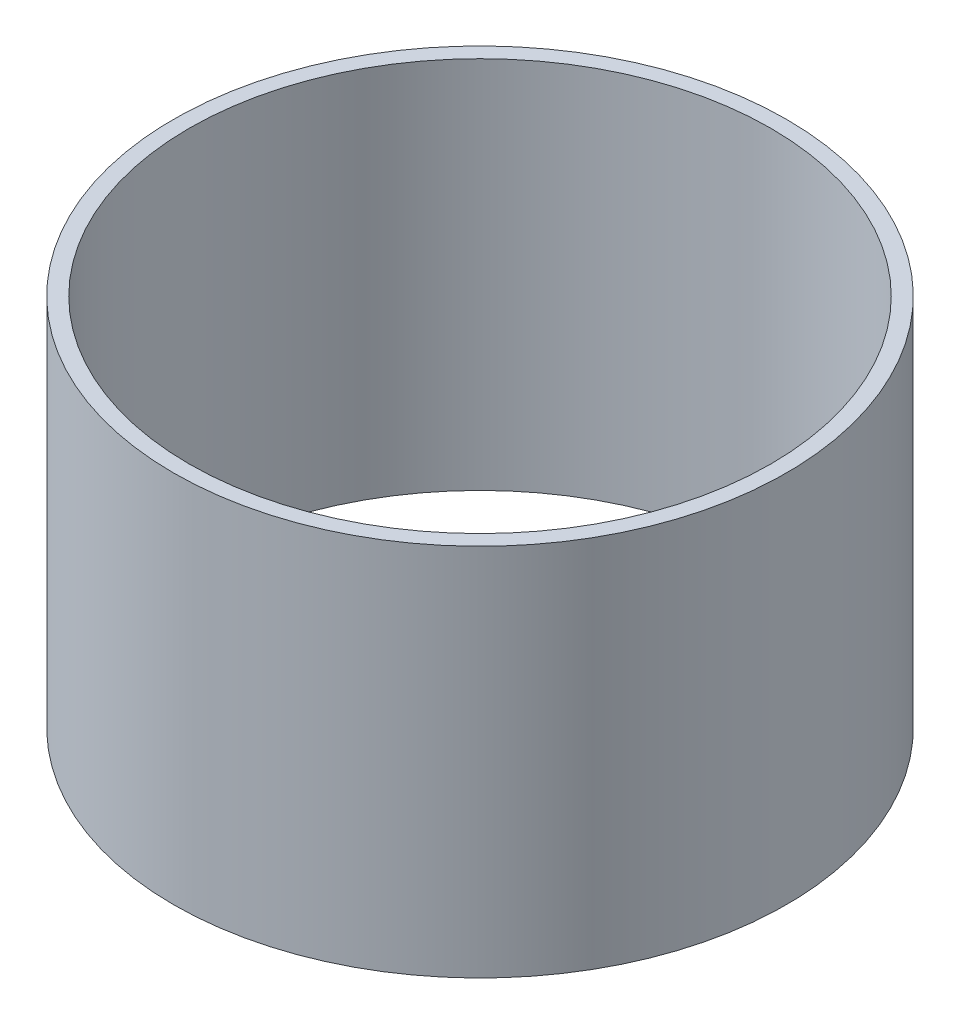
SolidWorks part; units mm, degrees
ref_plane "Front Plane" through (0, 0, 0) normal (0, 0, 1) x (1, 0, 0)
ref_plane "Top Plane" through (0, 0, 0) normal (0, 1, 0) x (1, 0, 0)
ref_plane "Right Plane" through (0, 0, 0) normal (1, 0, 0) x (0, 0, -1)
sketch "Sketch1" plane through (0, 0, 0) normal (0, 1, 0) x (1, 0, 0)
  circle A0 centre (0, 0) radius 93.6625
  circle A1 centre (0, 0) radius 88.9
  dimension "D1" = 187.325
  dimension "D2" = 177.8
extrude "Boss-Extrude1" add sketch "Sketch1" along normal mid plane 114.3025
